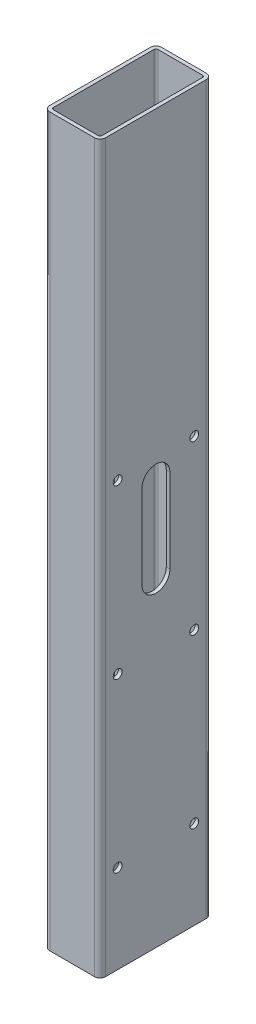
SolidWorks part; units mm, degrees
material "6061-T6 (SS)"
ref_plane "Front Plane" through (0, 0, 0) normal (0, 0, 1) x (1, 0, 0)
ref_plane "Top Plane" through (0, 0, 0) normal (0, 1, 0) x (1, 0, 0)
ref_plane "Right Plane" through (0, 0, 0) normal (1, 0, 0) x (0, 0, -1)
sketch "Sketch1" plane through (0, 0, 0) normal (0, 1, 0) x (1, 0, 0)
  line L1 (10.16, -25.4) -> (-10.16, -25.4)
  line L2 (12.7, -22.86) -> (12.7, 22.86)
  line L3 (10.16, 25.4) -> (-10.16, 25.4)
  line L4 (-12.7, -22.86) -> (-12.7, 22.86)
  line L5 (12.7, -25.4) -> (-12.7, 25.4) construction
  line L6 (12.7, 25.4) -> (-12.7, -25.4) construction
  arc A0 (-10.16, -25.4) -> (-12.7, -22.86) centre (-10.16, -22.86) cw
  arc A1 (10.16, -25.4) -> (12.7, -22.86) centre (10.16, -22.86) ccw
  arc A2 (12.7, 22.86) -> (10.16, 25.4) centre (10.16, 22.86) ccw
  arc A3 (-10.16, 25.4) -> (-12.7, 22.86) centre (-10.16, 22.86) ccw
  point P0 (0, 0)
  dimension "D3" = 2.54
  dimension "D1" = 25.4
  dimension "D2" = 50.8
extrude "Extrude-Thin1" add sketch "Sketch1" against normal blind 330.2 thin thin type one direction reverse wall 1.651
sketch "Sketch2" plane through (-12.7, 0, 0) normal (-1, 0, 0) x (0, 0, 1)
  line L0 (0, -146.2416) -> (0, -281.392) construction
  line L3 (-128.814, -427.442) -> (-122.464, -427.442) construction
  line L4 (6.6675, -146.2416) -> (6.6675, -281.392)
  line L5 (-6.6675, -146.2416) -> (-6.6675, -281.392)
  line L6 (-263.9645, -427.442) -> (-128.814, -427.442) construction
  line L7 (-128.814, -427.442) -> (0, -151.1994) construction
  line L8 (0, -275.042) -> (-263.9645, -427.442) construction
  arc A2 (6.6675, -146.2416) -> (-6.6675, -146.2416) centre (0, -146.2416) ccw
  arc A3 (-6.6675, -281.392) -> (6.6675, -281.392) centre (0, -281.392) ccw
  arc A4 (-122.464, -434.1095) -> (-122.464, -420.7745) centre (-122.464, -427.442) ccw construction
  point P2 (0, 0)
  point P3 (0, -213.8168)
  dimension "D5" = 13.335
  dimension "D2" = 65
  dimension "D3" = 30
  dimension "D4" = 304.8
  dimension "D6" = 6.35
extrude "Cut-Extrude1" cut sketch "Sketch2" against normal up to next
sketch "Sketch5" plane through (12.7, 0, 0) normal (1, 0, 0) x (0, 0, -1)
  line L0 (0, -146.2416) -> (0, -184.3416) construction
  line L1 (6.35, -146.2416) -> (6.35, -184.3416)
  line L2 (-6.35, -146.2416) -> (-6.35, -184.3416)
  arc A0 (6.35, -146.2416) -> (-6.35, -146.2416) centre (0, -146.2416) ccw
  arc A1 (-6.35, -184.3416) -> (6.35, -184.3416) centre (0, -184.3416) ccw
  arc A2 (6.6675, -146.2416) -> (-6.6675, -146.2416) centre (0, -146.2416) ccw construction
  point P2 (0, -165.2916)
  dimension "D1" = 6.35
  dimension "D2" = 38.1
extrude "Cut-Extrude4" cut sketch "Sketch5" against normal up to next
sketch "Sketch4" plane through (12.7, 0, 0) normal (1, 0, 0) x (0, 0, -1)
  circle A0 centre (-17.399, -290.0168) radius 2.0193 construction
  circle A1 centre (17.399, -290.0168) radius 2.0193 construction
  circle A2 centre (-17.399, -213.8168) radius 2.0193 construction
  circle A3 centre (17.399, -213.8168) radius 2.0193 construction
  circle A4 centre (-17.399, -137.6168) radius 2.0193 construction
  circle A5 centre (17.399, -137.6168) radius 2.0193 construction
  circle A6 centre (-17.399, -290.0168) radius 2.0193
  circle A7 centre (17.399, -290.0168) radius 2.0193
  circle A8 centre (-17.399, -213.8168) radius 2.0193
  circle A9 centre (17.399, -213.8168) radius 2.0193
  circle A10 centre (-17.399, -137.6168) radius 2.0193
  circle A11 centre (17.399, -137.6168) radius 2.0193
extrude "Cut-Extrude3" cut sketch "Sketch4" against normal through all
